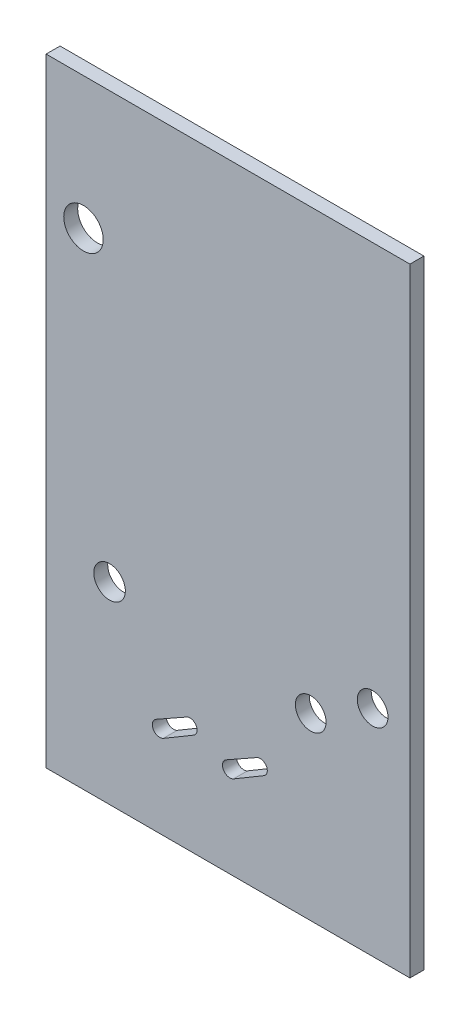
SolidWorks part; units mm, degrees
ref_plane "Front Plane" through (0, 0, 0) normal (0, 0, 1) x (1, 0, 0)
ref_plane "Top Plane" through (0, 0, 0) normal (0, 1, 0) x (1, 0, 0)
ref_plane "Right Plane" through (0, 0, 0) normal (1, 0, 0) x (0, 0, -1)
sketch "Sketch1" plane through (0, 0, 0) normal (0, 0, 1) x (1, 0, 0)
  line L0 (0.1058, 73.6301) -> (-0.0148, 62.4901) construction
  line L1 (-0.0148, 62.4901) -> (-0.0148, 56.2001) construction
  line L2 (-0.0148, 56.2001) -> (-0.0148, 10.268) construction
  line L3 (-15.4692, -49.8142) -> (-8.5409, -45.8142) construction
  line L4 (-15.4692, -49.8142) -> (0.5308, -49.8142) construction
  line L5 (0.5308, -49.8142) -> (7.4591, -45.8142) construction
  line L6 (-0.0148, 10.268) -> (0.1058, -73.6642) construction
  line L15 (-16.3293, -29.1587) -> (-16.3293, -23.8757)
  line L20 (-0.2968, -48.3429) -> (6.6759, -44.4208)
  line L21 (8.2583, -47.1985) -> (1.3584, -51.2855)
  line L22 (-44.5392, 73.6301) -> (44.7508, 73.6301)
  line L23 (44.7508, 73.6301) -> (44.7508, -73.6642)
  line L24 (44.7508, -73.6642) -> (-44.5392, -73.6642)
  line L25 (-44.5392, -73.6642) -> (-44.5392, 73.6301)
  line L26 (-25.0598, 56.2001) -> (-25.0598, 10.268)
  line L27 (-25.0598, 10.268) -> (25.0303, 10.268)
  line L28 (25.0303, 10.268) -> (25.0303, 56.2001)
  line L29 (25.0303, 56.2001) -> (-25.0598, 56.2001)
  line L34 (35.8896, 62.4901) -> (-35.9192, 62.4901)
  line L35 (-38.4192, 59.9901) -> (-38.4192, 6.918)
  line L36 (-35.9192, 4.418) -> (29.9974, 4.418)
  line L37 (38.3896, 13.668) -> (38.3896, 59.9901)
  line L38 (-16.2968, -48.3429) -> (-9.3241, -44.4208)
  line L39 (-7.7417, -47.1985) -> (-14.6416, -51.2855)
  line L150 (42.2525, -55.0539) -> (42.2511, -54.9499)
  circle A2 centre (-26.9008, -26.5172) radius 3.6
  arc A3 (8.2583, -47.1985) -> (6.6759, -44.4208) centre (7.4591, -45.8142) ccw
  arc A6 (-16.2968, -48.3429) -> (-14.6416, -51.2855) centre (-15.4692, -49.8142) ccw
  arc A7 (-7.7417, -47.1985) -> (-9.3241, -44.4208) centre (-8.5409, -45.8142) ccw
  circle A15 centre (18.9576, -29.5613) radius 3.5
  circle A16 centre (33.0683, -21.4917) radius 3.5
  arc A17 (-0.2968, -48.3429) -> (1.3584, -51.2855) centre (0.5308, -49.8142) ccw
  circle A19 centre (-32.8459, 40.326) radius 4.5
  arc A24 (38.3896, 59.9901) -> (35.8896, 62.4901) centre (35.8896, 59.9901) ccw
  arc A25 (-35.9192, 62.4901) -> (-38.4192, 59.9901) centre (-35.9192, 59.9901) ccw
  arc A26 (-38.4192, 6.918) -> (-35.9192, 4.418) centre (-35.9192, 6.918) ccw
  arc A27 (29.9974, 4.418) -> (38.3896, 13.668) centre (29.1397, 13.6282) ccw
  dimension "D4" = 11.14
  dimension "D8" = 7
  dimension "D11" = 9
  dimension "D12" = 7.2
  dimension "D14" = 9.25
  dimension "D15" = 2.5
  dimension "D2" = 89.29
  dimension "D3" = 147.2943
  dimension "D5" = 25.9097
  dimension "D6" = 8.0696
  dimension "D7" = 14.1107
  dimension "D9" = 7.7861
  dimension "D10" = 22.1641
  dimension "D13" = 10.5715
  dimension "D16" = 6.29
  dimension "D17" = 6.12
  dimension "D18" = 5.85
  dimension "D19" = 16
  dimension "D20" = 8
  dimension "D21" = 29.07
  dimension "D22" = 23.85
  dimension "D23" = 30
extrude "Bezel" add sketch "Sketch1<6>" along normal blind 3.18 contours L36 A27 L37 A24 L34 A25 L35 A26 L29 L28 L27 L26 A19 region at (36.9765, 61.077, 0)
sketch "Sketch1<6>" plane through (0, 0, 0) normal (0, 0, 1) x (1, 0, 0) same geometry as "Sketch1"
extrude "Body" add sketch "Sketch1" along normal blind 3.18 contours L25 L24 L23 L22 A27 L36 A26 L35 A25 L34 A24 L37 A17 L20 A3 L21 A16 A15 A7 L39 A6 L38 A2 region at (0.1688, -16.746, 0)
extrude "Boss-Extrude1" add sketch "Sketch1<11>" along normal blind 3.18 contours L28 L29 L26 L27 region at (-0.0148, 33.234, 0)
sketch "Sketch1<11>" plane through (0, 0, 0) normal (0, 0, 1) x (1, 0, 0) same geometry as "Sketch1"
sketch "Sketch2" plane through (0, 0, 3.18) normal (0, 0, 1) x (1, 0, 0)
  line L0 (-41.3592, 70.4501) -> (-41.3592, -70.4842)
  line L1 (-41.3592, -70.4842) -> (41.5708, -70.4842)
  line L2 (41.5708, -70.4842) -> (41.5708, 70.4501)
  line L3 (41.5708, 70.4501) -> (-41.3592, 70.4501)
  line L4 (-44.5392, 73.6301) -> (-44.5392, -73.6642)
  line L5 (-44.5392, -73.6642) -> (44.7508, -73.6642)
  line L6 (44.7508, -73.6642) -> (44.7508, 73.6301)
  line L7 (44.7508, 73.6301) -> (-44.5392, 73.6301)
  line L8 (-44.5392, 73.6301) -> (-44.5392, -73.6642)
  line L9 (-44.5392, -73.6642) -> (44.7508, -73.6642)
  line L10 (44.7508, -73.6642) -> (44.7508, 73.6301)
  line L11 (44.7508, 73.6301) -> (-44.5392, 73.6301)
  dimension "D1" = 0
  dimension "D2" = 3.18
extrude "Cut-Extrude1" cut sketch "Sketch2" against normal through all
